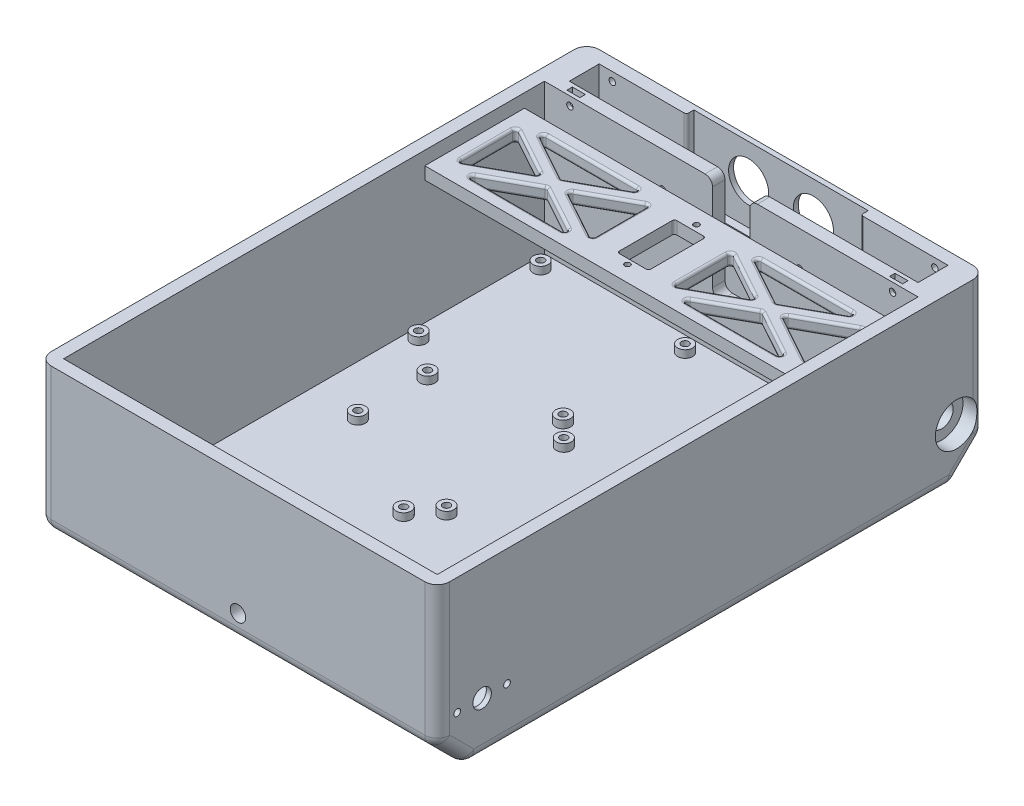
SolidWorks part; units mm, degrees
ref_plane "Front Plane" through (0, 0, 0) normal (0, 0, 1) x (1, 0, 0)
ref_plane "Top Plane" through (0, 0, 0) normal (0, 1, 0) x (1, 0, 0)
ref_plane "Right Plane" through (0, 0, 0) normal (1, 0, 0) x (0, 0, -1)
sketch "Main Body" plane through (0, 0, 0) normal (0, 1, 0) x (1, 0, 0)
  line L0 (-75, 110) -> (75, 110)
  line L1 (-75, -105) -> (75, -105)
  line L2 (-75, -105) -> (-75, 105)
  line L3 (-75, 105) -> (75, 105)
  line L4 (75, -105) -> (75, 105)
  line L5 (-75, -105) -> (75, 105) construction
  line L6 (-75, 105) -> (75, -105) construction
  line L7 (80, -105) -> (80, 105)
  line L8 (-75, -110) -> (75, -110)
  line L9 (-80, -105) -> (-80, 105)
  line L10 (-80, -110) -> (80, -110) construction
  line L11 (-80, -110) -> (-80, 110) construction
  line L12 (80, -110) -> (80, 110) construction
  line L13 (-80, 110) -> (80, 110) construction
  arc A0 (-75, -110) -> (-80, -105) centre (-75, -105) cw
  arc A1 (80, -105) -> (75, -110) centre (75, -105) cw
  arc A2 (75, 110) -> (80, 105) centre (75, 105) cw
  arc A3 (-75, 110) -> (-80, 105) centre (-75, 105) ccw
  point P0 (0, 0)
  dimension "D4" = 5
  dimension "D1" = 75
  dimension "D2" = 210
  dimension "D3" = 5
extrude "Boss-Extrude1" add sketch "Main Body" along normal blind 8 contours L1 L4 L3 L2 | L9 L8 L7 L0 L4 L1 L2 L3 region at (0, 0, -107.2797) region at (0, 0, 0)
extrude "Boss-Extrude3" add sketch "Main Body<4>" along normal blind 60 from surface starting at face at (0, 8, 0)
sketch "Main Body<4>" plane through (0, 0, 0) normal (0, 1, 0) x (1, 0, 0) same geometry as "Main Body"
sketch "Sketch1" plane through (75, 0, 0) normal (-1, 0, 0) x (0, 0, 1)
  line L0 (105, 68) -> (105, 8) construction
  line L1 (-105, 8) -> (105, 8) construction
  line L2 (79, 15.5) -> (105, 15.5)
  line L3 (79, 8) -> (105, 8)
  line L4 (79, 8) -> (79, 34)
  line L5 (79, 34) -> (105, 34)
  line L6 (105, 8) -> (105, 34)
  line L7 (79, 8) -> (105, 34) construction
  line L8 (79, 34) -> (105, 8) construction
  circle A0 centre (92, 21) radius 13
  line M2 (-105, 8) -> (105, 8)
  line M3 (105, 8) -> (105, 68)
  dimension "D1" = 26
  dimension "D2" = 7.5
extrude "Boss-Extrude4" add sketch "Sketch1" along normal up to surface (150 mm away) contours A0 L4 M2 | A0 L3 M3 region at (75, 10.5201, 82.0674) region at (75, 10.5201, 101.9326) up to face at (-75, 38, 0)
sketch "Sketch2" plane through (0, 0, 0) normal (1, 0, 0) x (0, 0, -1)
  line L0 (-105, 68) -> (-105, 15.5) construction
  line L1 (-105, 8) -> (-79, 8)
  line L2 (-105, 8) -> (-105, 15.5)
  line L3 (-105, 15.5) -> (-79, 15.5)
  line L4 (-79, 8) -> (-79, 15.5)
  line L5 (105, 8) -> (-79, 8) construction
  line L6 (-79, 8) -> (-79, 15.5) construction
  line L7 (-79, 15.5) -> (-80.2208, 15.5) construction
extrude "Cut-Extrude1" cut sketch "Sketch2" against normal mid plane 12
sketch "Sketch3" plane through (0, 8, 0) normal (0, 1, 0) x (1, 0, 0)
  line L0 (75, -105) -> (-75, -105) construction
  line L1 (-4, -79) -> (-11, -79)
  line L2 (-4, -79) -> (-4, -105)
  line L3 (-4, -105) -> (-11, -105)
  line L4 (-11, -79) -> (-11, -105)
  line L5 (0, 0) -> (0, -105) construction
  line L6 (-75, -79) -> (-6, -79) construction
  line L7 (11, -79) -> (11, -105)
  line L8 (4, -105) -> (11, -105)
  line L9 (4, -79) -> (4, -105)
  line L10 (4, -79) -> (11, -79)
  line L11 (-6, -103.7792) -> (-6, -92) construction
  dimension "D1" = 5
  dimension "D2" = 4
extrude "Boss-Extrude5" add sketch "Sketch3" along normal blind 20
sketch "Sketch4" plane through (0, 8, 0) normal (0, 1, 0) x (1, 0, 0)
  line L0 (-75, -105) -> (-75, 105) construction
  line L1 (-75, 93) -> (75, 93)
  line L2 (-75, 93) -> (-75, 88)
  line L3 (-75, 88) -> (75, 88)
  line L4 (75, 93) -> (75, 88)
  line L5 (75, 105) -> (75, -105) construction
  line L6 (-75, 105) -> (75, 105) construction
  dimension "D1" = 17
  dimension "D2" = 5
extrude "Boss-Extrude6" add sketch "Sketch4" along normal up to surface (60 mm away) up to face at (0, 68, 0)
sketch "Sketch5" plane through (80, 0, 0) normal (1, 0, 0) x (0, 0, -1)
  circle A0 centre (-92, 21) radius 3.5 construction
  circle A1 centre (-92, 21) radius 3.5
  circle A2 centre (-92, 21) radius 3.7
  dimension "D1" = 0.2
extrude "Cut-Extrude4" cut sketch "Sketch5" against normal up to next contours A1 | A2 A1 region at (80, 21, 92) region at (80, 21, 95.5953)
sketch "Sketch6" plane through (-75, 0, 0) normal (1, 0, 0) x (0, 0, -1)
  circle A0 centre (-92, 21) radius 13
  dimension "D1" = 26
extrude "Cut-Extrude5" cut sketch "Sketch6" against normal offset from surface (3 mm away) 2 up to face at (-80, 34, 0)
mirror "Mirror1" about plane through (0, 0, 0) normal (1, 0, 0) of "Cut-Extrude4"
sketch "Sketch8" plane through (75, 0, 0) normal (-1, 0, 0) x (0, 0, 1)
  circle A0 centre (92, 21) radius 13
  dimension "D1" = 26
extrude "Cut-Extrude6" cut sketch "Sketch8" against normal offset from surface (3 mm away) 2 up to face at (80, 21, 88.3)
sketch "Sketch10" plane through (80, 0, 0) normal (1, 0, 0) x (0, 0, -1)
  circle A1 centre (-82, 21) radius 1.25
  circle A2 centre (-82, 21) radius 1.25
  circle A3 centre (-102, 21) radius 1.25
  circle A4 centre (-102, 21) radius 1.25
  circle A5 centre (-92, 21) radius 12.5
  circle A6 centre (-92, 21) radius 12.5
  circle A63 centre (-102, 21) radius 1.35
  circle A64 centre (-82, 21) radius 1.35
  dimension "D1" = 0
  dimension "D2" = 0
  dimension "D3" = 0
  dimension "D4" = 0.1
  dimension "D5" = 0.1
extrude "Cut-Extrude7" cut sketch "Sketch10" against normal up to next contours A2 | A64 A2 | A4 | A63 A4 region at (80, 21, 82) region at (80, 21, 102) region at (80, 21, 103.3118) region at (80, 21, 83.3118)
mirror "Mirror3" about plane through (0, 0, 0) normal (1, 0, 0) of "Cut-Extrude7"
sketch "Sketch11" plane through (80, 0, 0) normal (1, 0, 0) x (0, 0, -1)
  circle A0 centre (98.5, 21) radius 4.5 construction
  circle A1 centre (98.5, 21) radius 4.5
  circle A3 centre (98.5, 21) radius 4.6
  dimension "D1" = 0.1
extrude "Cut-Extrude10" cut sketch "Sketch11" against normal through all contours A1 | A3 A1 region at (80, 21, -98.5) region at (80, 21, -93.913)
sketch "Sketch12" plane through (-75, 0, 0) normal (1, 0, 0) x (0, 0, -1)
  line L0 (93, 8) -> (105, 8) construction
  line L1 (93, 68) -> (105, 68)
  line L2 (93, 68) -> (93, 8)
  line L3 (93, 8) -> (105, 8)
  line L4 (105, 68) -> (105, 8)
  line L6 (93, 68) -> (93, 8) construction
  line L7 (93, 68) -> (105, 68) construction
  circle A2 centre (98.5, 21) radius 4.6 construction
  circle A3 centre (98.5, 21) radius 4.6
extrude "Boss-Extrude7" add sketch "Sketch12" along normal blind 5
sketch "Sketch13" plane through (-80, 0, 0) normal (-1, 0, 0) x (0, 0, 1)
  circle A0 centre (-98.5, 21) radius 8.55
  circle A2 centre (-98.5, 21) radius 4.6 construction
  dimension "D1" = 17.1
extrude "Cut-Extrude11" cut sketch "Sketch13" against normal blind 6
mirror "Mirror4" about plane through (0, 0, 0) normal (1, 0, 0) of "Boss-Extrude7", "Cut-Extrude11"
sketch "Sketch14" plane through (0, 8, 0) normal (0, 1, 0) x (1, 0, 0)
  line L0 (-4, -105) -> (-4, -79) construction
  line L1 (-4, -95) -> (4, -95)
  line L2 (-4, -95) -> (-4, -105)
  line L3 (-4, -105) -> (4, -105)
  line L4 (4, -95) -> (4, -105)
  dimension "D1" = 10
extrude "Boss-Extrude9" add sketch "Sketch14" along normal blind 5
sketch "Sketch15" plane through (0, 0, 110) normal (0, 0, 1) x (1, 0, 0)
  arc A0 (-3, 19.5) -> (3, 19.5) centre (0, 19.5) ccw construction
  arc A1 (-3, 19.5) -> (3, 19.5) centre (0, 19.5) ccw
  arc A2 (3, 19.5) -> (-3, 19.5) centre (0, 19.5) ccw construction
  arc A3 (3, 19.5) -> (-3, 19.5) centre (0, 19.5) ccw
  arc A4 (3.1, 19.5) -> (-3.1, 19.5) centre (0, 19.5) ccw
  arc A5 (-3.1, 19.5) -> (3.1, 19.5) centre (0, 19.5) ccw
  dimension "D1" = 0.1
extrude "Cut-Extrude12" cut sketch "Sketch15" against normal up to next contours A1 A3 | A4 A5 A3 A1 region at (0, 19.5, 110) region at (0, 16.4877, 110)
sketch "Sketch16" plane through (0, 0, 0) normal (0, -1, 0) x (1, 0, 0)
  circle A0 centre (-12.5, -82) radius 1.475 construction
  circle A1 centre (-70.5, -82) radius 1.475 construction
  circle A2 centre (-70.5, -33) radius 1.475 construction
  circle A3 centre (-12.5, -33) radius 1.475 construction
  circle A4 centre (-4.2, -25) radius 1.475 construction
  circle A5 centre (-55, -21.12) radius 1.475 construction
  circle A6 centre (-55, 6.88) radius 1.475 construction
  circle A7 centre (-4.2, 22.08) radius 1.475 construction
  circle A8 centre (-12.3, 31.18) radius 1.475 construction
  circle A9 centre (24.2, 31.18) radius 1.475 construction
  circle A10 centre (37.8459, 24.117) radius 1.475 construction
  circle A11 centre (59.5541, 24.117) radius 1.475 construction
  circle A12 centre (59.5541, 68.243) radius 1.475 construction
  circle A13 centre (37.8459, 68.243) radius 1.475 construction
  circle A14 centre (24.2, 67.68) radius 1.475 construction
  circle A15 centre (-12.3, 67.68) radius 1.475 construction
  circle A16 centre (-12.5, -82) radius 1.475
  circle A17 centre (-70.5, -82) radius 1.475
  circle A18 centre (-70.5, -33) radius 1.475
  circle A19 centre (-12.5, -33) radius 1.475
  circle A20 centre (-4.2, -25) radius 1.475
  circle A21 centre (-55, -21.12) radius 1.475
  circle A22 centre (-55, 6.88) radius 1.475
  circle A23 centre (-4.2, 22.08) radius 1.475
  circle A24 centre (-12.3, 31.18) radius 1.475
  circle A25 centre (24.2, 31.18) radius 1.475
  circle A26 centre (37.8459, 24.117) radius 1.475
  circle A27 centre (59.5541, 24.117) radius 1.475
  circle A28 centre (59.5541, 68.243) radius 1.475
  circle A29 centre (37.8459, 68.243) radius 1.475
  circle A30 centre (24.2, 67.68) radius 1.475
  circle A31 centre (-12.3, 67.68) radius 1.475
extrude "Cut-Extrude13" cut sketch "Sketch16" against normal up to next
sketch "Sketch17" plane through (0, 8, 0) normal (0, 1, 0) x (1, 0, 0)
  line L0 (0, 88) -> (0, -110) construction
  line L1 (-75, 88) -> (75, 88) construction
  line L2 (75, -110) -> (-75, -110) construction
  line L3 (-75, 4.5) -> (75, 4.5) construction
  line L7 (-75, -79) -> (-75, 88) construction
  line L8 (75, 88) -> (75, -79) construction
  circle A0 centre (-70.5, 82) radius 3
  circle A1 centre (-12.5, 82) radius 3
  circle A2 centre (-12.3, -67.68) radius 1.475
  circle A3 centre (-12.3, -67.68) radius 1.475
  circle A4 centre (24.2, -67.68) radius 1.475
  circle A5 centre (24.2, -67.68) radius 1.475
  circle A6 centre (37.8459, -68.243) radius 1.475
  circle A7 centre (37.8459, -68.243) radius 1.475
  circle A8 centre (59.5541, -68.243) radius 1.475
  circle A9 centre (59.5541, -68.243) radius 1.475
  circle A10 centre (59.5541, -24.117) radius 1.475
  circle A11 centre (59.5541, -24.117) radius 1.475
  circle A12 centre (37.8459, -24.117) radius 1.475
  circle A13 centre (37.8459, -24.117) radius 1.475
  circle A14 centre (24.2, -31.18) radius 1.475
  circle A15 centre (24.2, -31.18) radius 1.475
  circle A16 centre (-12.3, -31.18) radius 1.475
  circle A17 centre (-12.3, -31.18) radius 1.475
  circle A18 centre (-4.2, -22.08) radius 1.475
  circle A19 centre (-4.2, -22.08) radius 1.475
  circle A20 centre (-55, -6.88) radius 1.475
  circle A21 centre (-55, -6.88) radius 1.475
  circle A22 centre (-55, 21.12) radius 1.475
  circle A23 centre (-55, 21.12) radius 1.475
  circle A24 centre (-4.2, 25) radius 1.475
  circle A25 centre (-4.2, 25) radius 1.475
  circle A26 centre (-12.5, 33) radius 1.475
  circle A27 centre (-12.5, 33) radius 1.475
  circle A28 centre (-70.5, 33) radius 1.475
  circle A29 centre (-70.5, 33) radius 1.475
  circle A30 centre (-70.5, 82) radius 1.475
  circle A31 centre (-70.5, 82) radius 1.475
  circle A32 centre (-12.5, 82) radius 1.475
  circle A33 centre (-12.5, 82) radius 1.475
  circle A34 centre (-70.5, 33) radius 3
  circle A35 centre (-55, 21.12) radius 3
  circle A36 centre (-12.5, 33) radius 3
  circle A37 centre (-4.2, 25) radius 3
  circle A38 centre (-55, -6.88) radius 3
  circle A39 centre (-4.2, -22.08) radius 3
  circle A40 centre (-12.3, -31.18) radius 3
  circle A41 centre (24.2, -31.18) radius 3
  circle A42 centre (37.8459, -24.117) radius 3
  circle A43 centre (59.5541, -24.117) radius 3
  circle A44 centre (-12.3, -67.68) radius 3
  circle A45 centre (24.2, -67.68) radius 3
  circle A46 centre (37.8459, -68.243) radius 3
  circle A47 centre (59.5541, -68.243) radius 3
  dimension "D1" = 6
  dimension "D2" = 0
  dimension "D3" = 0
  dimension "D4" = 0
  dimension "D5" = 0
  dimension "D6" = 0
  dimension "D7" = 0
  dimension "D8" = 0
  dimension "D9" = 0
  dimension "D10" = 0
  dimension "D11" = 0
  dimension "D12" = 0
  dimension "D13" = 0
  dimension "D14" = 0
  dimension "D15" = 0
  dimension "D16" = 0
  dimension "D17" = 0
extrude "Boss-Extrude10" add sketch "Sketch17" along normal blind 3
sketch "Sketch18" plane through (75, 0, 0) normal (-1, 0, 0) x (0, 0, 1)
  line L1 (-80, 62.6) -> (-40, 62.6)
  line L2 (-80, 62.6) -> (-80, 57.6)
  line L3 (-80, 57.6) -> (-40, 57.6)
  line L4 (-40, 62.6) -> (-40, 57.6)
  line L5 (-88, 68) -> (105, 68) construction
  dimension "D1" = 5
  dimension "D2" = 30
  dimension "D3" = 40
  dimension "D4" = 5.4
extrude "Boss-Extrude11" add sketch "Sketch18" along normal up to next
sketch "Sketch19" plane through (0, 68, 0) normal (0, 1, 0) x (1, 0, 0)
  line L1 (-6.3, 71.5) -> (6.3, 71.5)
  line L2 (-6.3, 71.5) -> (-6.3, 48.5)
  line L3 (-6.3, 48.5) -> (6.3, 48.5)
  line L4 (6.3, 71.5) -> (6.3, 48.5)
  line L12 (-75, 80) -> (-75, 40)
  line L13 (-75, 40) -> (75, 40)
  line L14 (75, 40) -> (75, 80)
  line L15 (75, 80) -> (-75, 80)
  line L16 (-75, 80) -> (-75, 40)
  line L17 (-75, 40) -> (75, 40)
  line L18 (75, 40) -> (75, 80)
  line L19 (75, 80) -> (-75, 80)
  point P4 (0, 71.5)
  point P8 (0, 80)
  point P12 (6.3, 60)
  point P13 (75, 60)
  dimension "D1" = 23
  dimension "D2" = 12.6
  dimension "D3" = 0
extrude "Cut-Extrude14" cut sketch "Sketch19" against normal up to next contours L4 L1 L2 L3 region at (0, 68, -60)
sketch "Sketch21" plane through (0, 0, -110) normal (0, 0, -1) x (-1, 0, 0)
  circle A1 centre (-64.75, 64.5) radius 1.3
  circle A2 centre (-64.75, 64.5) radius 1.3
  circle A3 centre (64.75, 64.5) radius 1.3
  circle A4 centre (64.75, 64.5) radius 1.3
  dimension "D1" = 0
  dimension "D2" = 0
extrude "Cut-Extrude16" cut sketch "Sketch21" against normal up to surface (22 mm away) up to face at (0, 38, -88)
ref_plane "Plane1" through (0, 0, -90.5) normal (0, 0, -1) x (-1, 0, 0)
sketch "Sketch22" plane through (0, 0, -90.5) normal (0, 0, -1) x (-1, 0, 0)
  line L0 (-67.35, 66.0011) -> (-67.35, 68)
  line L1 (-62.15, 66.0011) -> (-64.75, 67.5022)
  line L2 (-64.75, 67.5022) -> (-67.35, 66.0011)
  line L3 (-67.35, 66.0011) -> (-67.35, 62.9989)
  line L4 (-67.35, 62.9989) -> (-64.75, 61.4978)
  line L5 (-64.75, 61.4978) -> (-62.15, 62.9989)
  line L6 (-62.15, 62.9989) -> (-62.15, 66.0011)
  line L7 (-67.35, 68) -> (-62.15, 68)
  line L8 (-62.15, 68) -> (-62.15, 66.0011)
  line L9 (70, 68) -> (-70, 68) construction
  line L10 (0, 0) -> (0, 68) construction
  line L11 (75, 68) -> (-75, 68) construction
  line L12 (64.75, 61.4978) -> (62.15, 62.9989)
  line L13 (67.35, 62.9989) -> (64.75, 61.4978)
  line L14 (64.75, 67.5022) -> (67.35, 66.0011)
  line L15 (67.35, 66.0011) -> (67.35, 62.9989)
  line L16 (67.35, 66.0011) -> (67.35, 68)
  line L17 (62.15, 62.9989) -> (62.15, 66.0011)
  line L18 (62.15, 68) -> (62.15, 66.0011)
  line L19 (67.35, 68) -> (62.15, 68)
  line L20 (62.15, 66.0011) -> (64.75, 67.5022)
  circle A0 centre (-64.75, 64.5) radius 2.6 construction
  dimension "D1" = 5.2
extrude "Cut-Extrude17" cut sketch "Sketch22" against normal mid plane 2.2 contours L20 L17 L12 L13 L15 L14 | L18 L20 L14 L16 L19 | L5 L6 L1 L2 L3 L4 | L8 L7 L0 L2 L1 region at (67.2943, 67.0006, -90.5) region at (64.75, 64.5, -90.5) region at (-64.75, 64.5, -90.5) region at (-62.2057, 67.0006, -90.5)
sketch "Sketch23" plane through (0, 0, -110) normal (0, 0, -1) x (-1, 0, 0)
  circle A0 centre (64.75, 64.5) radius 2.5
  circle A1 centre (-64.75, 64.5) radius 2.5
  dimension "D1" = 5
  dimension "D2" = 5
extrude "Cut-Extrude18" cut sketch "Sketch23" against normal mid plane 2.5
sketch "Sketch24" plane through (0, 62.6, 0) normal (0, 1, 0) x (1, 0, 0)
  circle A0 centre (0, 46.35) radius 1.1002
  arc A1 (0.4, 45.4333) -> (-0.4, 45.4333) centre (0, 46.35) ccw construction
  circle A2 centre (0, 74.05) radius 1.1002
  arc A3 (-0.4, 74.9667) -> (0, 73.0498) centre (0, 74.05) ccw construction
  point P5 (0.4, 45.4333)
  dimension "D1" = 0.1
extrude "Cut-Extrude19" cut sketch "Sketch24" against normal up to next
sketch "Sketch25" plane through (0, 62.6, 0) normal (0, 1, 0) x (1, 0, 0)
  line L0 (6.3, 71.5) -> (6.3, 48.5) construction
  line L1 (-11.3, 80) -> (11.3, 80)
  line L2 (-11.3, 80) -> (-11.3, 40)
  line L3 (-11.3, 40) -> (11.3, 40)
  line L4 (-75, 80) -> (-75, 40)
  line L5 (-75, 40) -> (75, 40)
  line L6 (75, 40) -> (75, 80)
  line L7 (75, 80) -> (-75, 80)
  line L8 (-75, 80) -> (-75, 40)
  line L9 (-75, 40) -> (75, 40)
  line L10 (75, 40) -> (75, 80)
  line L11 (75, 80) -> (-75, 80)
  line L12 (11.3, 80) -> (11.3, 40)
  line L13 (-11.3, 80) -> (11.3, 40) construction
  line L14 (-11.3, 40) -> (11.3, 80) construction
  line L15 (0, 80) -> (0, 40) construction
  line L16 (70, 75) -> (70, 45)
  line L17 (-70, 75) -> (-16.3, 75)
  line L18 (-70, 75) -> (-70, 45)
  line L19 (-70, 45) -> (-16.3, 45)
  line L20 (-16.3, 75) -> (-16.3, 45)
  line L21 (-70, 75) -> (-16.3, 45) construction
  line L22 (-70, 45) -> (-16.3, 75) construction
  line L23 (70, 75) -> (16.3, 45) construction
  line L24 (70, 45) -> (16.3, 75) construction
  line L25 (70, 75) -> (16.3, 75)
  line L26 (16.3, 75) -> (16.3, 45)
  line L27 (70, 45) -> (16.3, 45)
  line L28 (-75, 60) -> (-11.3, 60) construction
  line L29 (75, 60) -> (11.3, 60) construction
  line L30 (-70, 71.9362) -> (-48.3314, 60)
  line L31 (-16.3, 71.9362) -> (-37.9686, 60)
  line L32 (70, 71.9362) -> (48.3314, 60)
  line L33 (-48.3314, 60) -> (-70, 48.0638)
  line L34 (48.3314, 60) -> (70, 48.0638)
  line L35 (-65.199, 45) -> (-43.15, 57.1458)
  line L36 (65.199, 45) -> (43.15, 57.1458)
  line L37 (-43.15, 57.1458) -> (-21.101, 45)
  line L38 (43.15, 57.1458) -> (21.101, 45)
  line L39 (16.3, 71.9362) -> (37.9686, 60)
  line L40 (-37.9686, 60) -> (-16.3, 48.0638)
  line L41 (37.9686, 60) -> (16.3, 48.0638)
  line L42 (-65.199, 75) -> (-43.15, 62.8542)
  line L43 (65.199, 75) -> (43.15, 62.8542)
  line L44 (-43.15, 62.8542) -> (-21.101, 75)
  line L45 (43.15, 62.8542) -> (21.101, 75)
  line L46 (-75, 40) -> (-75, 80) construction
  line L47 (-75, 40) -> (75, 40) construction
  point P2 (0, 60)
  point P9 (-43.15, 60)
  point P10 (75, 60)
  point P24 (43.15, 60)
  point P62 (-54.1745, 68.9271)
  dimension "D2" = 5
  dimension "D3" = 5
  dimension "D4" = 5
  dimension "D5" = 5
  dimension "D6" = 26.6686
  dimension "D1" = 0
extrude "Cut-Extrude21" cut sketch "Sketch25" against normal up to next contours L37 L35 L19 | L33 L30 L18 | L42 L44 L17 | L31 L40 L20 | L41 L39 L26 | L45 L43 L25 | L36 L38 L27 | L32 L34 L16 region at (62.7771, 62.6, -60) region at (43.15, 62.6, -70.9514) region at (43.15, 62.6, -49.0486) region at (23.5229, 62.6, -60) region at (-43.15, 62.6, -70.9514) region at (-62.7771, 62.6, -60) region at (-23.5229, 62.6, -60) region at (-43.15, 62.6, -49.0486)
sketch "Sketch26" plane through (-80, 0, 0) normal (-1, 0, 0) x (0, 0, 1)
  line L0 (-110, 12.58) -> (-97.42, 0)
  line L1 (-110, 68) -> (-110, 0) construction
  line L2 (105, 0) -> (-105, 0) construction
  line L3 (-97.42, 0) -> (-92.42, 0)
  line L4 (-92.42, 0) -> (-110, 17.58)
  line L5 (-110, 17.58) -> (-110, 12.58)
  line L6 (-110, 12.58) -> (-110, 0)
  line L7 (-110, 0) -> (-97.42, 0)
  circle A1 centre (-98.5, 21) radius 8.55 construction
  line M5 (-105, 15.4455) -> (-105, 0)
  line M6 (-105, 0) -> (105, 0)
  dimension "D1" = 2
  dimension "D2" = 5
  dimension "D3" = 45
extrude "Cut-Extrude22" cut sketch "Sketch26" against normal up to next contours L6 L7 L0 M5 | L0 M5 M6 region at (-80, 5.1434, -107.7067) region at (-80, 2.5267, -102.4733)
mirror "Mirror5" about plane through (0, 0, 0) normal (0, 0, 1) of "Cut-Extrude22"
fillet "Fillet1" radius 5 14 edges at (80, 3.79, -101.21) (78.5355, 11.1156, -108.5355) (-80, 3.79, -101.21) (-78.5355, 11.1156, -108.5355) (80, 3.79, 101.21) (78.5355, 11.1156, 108.5355) (-80, 3.79, 101.21) (-78.5355, 11.1156, 108.5355) (0, 0, -97.42) (0, 12.58, -110) (0, 0, 97.42) (0, 12.58, 110) (-80, 0, 0) (80, 0, 0)
fillet "Fillet2" radius 1 76 edges at (-32.1255, 57.6, -51.0729) (-32.1255, 62.6, -51.0729) (-21.101, 60.1, -45) (-43.15, 62.6, -45) (-43.15, 57.6, -45) (-54.1745, 57.6, -51.0729) (-65.199, 60.1, -45) (-54.1745, 62.6, -51.0729) (-43.15, 60.1, -57.1458) (32.1255, 57.6, -68.9271) (32.1255, 62.6, -68.9271) (21.101, 60.1, -75) (43.15, 62.6, -75) (43.15, 57.6, -75) (54.1745, 57.6, -68.9271) (65.199, 60.1, -75) (54.1745, 62.6, -68.9271) (43.15, 60.1, -62.8542) (54.1745, 62.6, -51.0729) (54.1745, 57.6, -51.0729) (43.15, 57.6, -45) (65.199, 60.1, -45) (43.15, 62.6, -45) (21.101, 60.1, -45) (32.1255, 62.6, -51.0729) (43.15, 60.1, -57.1458) (32.1255, 57.6, -51.0729) (59.1657, 62.6, -65.9681) (59.1657, 57.6, -65.9681) (70, 57.6, -60) (70, 60.1, -71.9362) (70, 62.6, -60) (70, 60.1, -48.0638) (59.1657, 62.6, -54.0319) (48.3314, 60.1, -60) (59.1657, 57.6, -54.0319) (-54.1745, 62.6, -68.9271) (-54.1745, 57.6, -68.9271) (-43.15, 57.6, -75) (-65.199, 60.1, -75) (-43.15, 62.6, -75) (-21.101, 60.1, -75) (-32.1255, 62.6, -68.9271) (-43.15, 60.1, -62.8542) (-32.1255, 57.6, -68.9271) (-59.1657, 57.6, -54.0319) (-59.1657, 62.6, -54.0319) (-70, 60.1, -48.0638) (-70, 62.6, -60) (-70, 57.6, -60) (-59.1657, 57.6, -65.9681) (-70, 60.1, -71.9362) (-59.1657, 62.6, -65.9681) (-48.3314, 60.1, -60) (-27.1343, 62.6, -65.9681) (-27.1343, 57.6, -65.9681) (-16.3, 57.6, -60) (-16.3, 60.1, -71.9362) (-16.3, 62.6, -60) (-16.3, 60.1, -48.0638) (-27.1343, 62.6, -54.0319) (-37.9686, 60.1, -60) (-27.1343, 57.6, -54.0319) (27.1343, 57.6, -54.0319) (27.1343, 62.6, -54.0319) (16.3, 60.1, -48.0638) (16.3, 62.6, -60) (16.3, 57.6, -60) (27.1343, 57.6, -65.9681) (16.3, 60.1, -71.9362) (27.1343, 62.6, -65.9681) (37.9686, 60.1, -60) (6.3, 60.1, -48.5) (-6.3, 60.1, -48.5) (-6.3, 60.1, -71.5) (6.3, 60.1, -71.5)
sketch "Sketch33" plane through (0, 0, -110) normal (0, 0, -1) x (-1, 0, 0)
  circle A0 centre (-13, 53.9999) radius 8.05
  circle A1 centre (13, 53.9999) radius 8.05
  circle A2 centre (-13, 53.9999) radius 7.3 construction
  circle A3 centre (13, 53.9999) radius 7.3 construction
  dimension "D1" = 16.1
extrude "Cut-Extrude27" cut sketch "Sketch33" against normal up to next
sketch "Sketch34" plane through (0, 0, -93) normal (0, 0, -1) x (-1, 0, 0)
  circle A0 centre (27.525, 54) radius 1.3 construction
  circle A1 centre (27.525, 54) radius 1.3
  circle A2 centre (-27.525, 54) radius 1.3 construction
  circle A3 centre (-27.525, 54) radius 1.3
extrude "Cut-Extrude28" cut sketch "Sketch34" against normal up to next
sketch "Sketch35" plane through (0, 68, 0) normal (0, 1, 0) x (1, 0, 0)
  line L0 (70, 93) -> (-70, 93) construction
  line L1 (-7.5, 93) -> (7.5, 93)
  line L2 (-7.5, 93) -> (-7.5, 88)
  line L3 (-7.5, 88) -> (7.5, 88)
  line L4 (7.5, 93) -> (7.5, 88)
  line L5 (-7.5, 93) -> (7.5, 88) construction
  line L6 (-7.5, 88) -> (7.5, 93) construction
  line L7 (-75, 88) -> (75, 88) construction
  point P0 (0, 90.5)
  dimension "D1" = 15
extrude "Cut-Extrude29" cut sketch "Sketch35" against normal offset from surface (41 mm away) 19 up to face at (37.8459, 8, 71.243)
fillet "Fillet4" radius 3 9 edges at (0, 8, 95) (-7.5, 28, 79) (-7.5, 28, 105) (7.5, 28, 105) (7.5, 28, 79) (-7.5, 68, -90.5) (7.5, 68, -90.5) (-7.5, 27, -90.5) (7.5, 27, -90.5)
fillet "Fillet5" radius 1 1 edges at (0, 13, 95)
sketch "Sketch36" plane through (0, 68, 0) normal (0, 1, 0) x (1, 0, 0)
  line L0 (-70, 105) -> (70, 105) construction
  line L1 (-35, 108) -> (35, 108)
  line L2 (-35, 108) -> (-35, 105)
  line L3 (-35, 105) -> (35, 105)
  line L4 (35, 108) -> (35, 105)
  line L5 (-75, 110) -> (75, 110) construction
  point P6 (0, 108)
  dimension "D1" = 70
  dimension "D2" = 2
extrude "Cut-Extrude30" cut sketch "Sketch36" against normal blind 30
fillet "Fillet6" radius 1 2 edges at (35, 53, -105) (-35, 53, -105)
